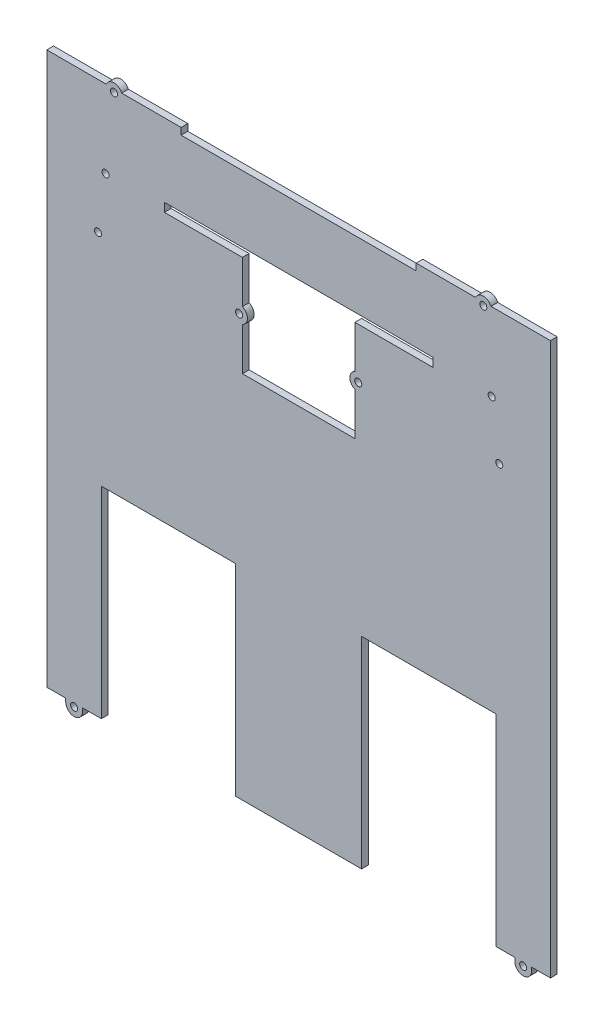
SolidWorks part; units mm, degrees
ref_plane "Plan de face" through (0, 0, 0) normal (0, 0, 1) x (1, 0, 0)
ref_plane "Plan de dessus" through (0, 0, 0) normal (0, 1, 0) x (1, 0, 0)
ref_plane "Plan de droite" through (0, 0, 0) normal (1, 0, 0) x (0, 0, -1)
sketch "Esquisse1" plane through (0, 0, 0) normal (0, 0, 1) x (1, 0, 0)
  line L1 (150, -140) -> (-150, -140)
  line L2 (150, -140) -> (150, 140)
  line L3 (150, 140) -> (-150, 140)
  line L4 (-150, -140) -> (-150, 140)
  line L5 (150, -140) -> (-150, 140) construction
  line L6 (150, 140) -> (-150, -140) construction
  point P0 (0, 0)
  dimension "D1" = 280
  dimension "D2" = 300
extrude "Boss.-Extru.1" add sketch "Esquisse1" along normal blind 4
sketch "Esquisse2" plane through (0, 0, 4) normal (0, 0, 1) x (1, 0, 0)
  line L0 (0, 0) -> (0, -140) construction
  line L1 (-150, -140) -> (150, -140) construction
  line L2 (117.5, -140) -> (117.5, -20)
  line L3 (-37.5, -140) -> (-117.5, -140)
  line L4 (-37.5, -140) -> (-37.5, -20)
  line L5 (-37.5, -20) -> (-117.5, -20)
  line L6 (-117.5, -140) -> (-117.5, -20)
  line L7 (37.5, -20) -> (117.5, -20)
  line L8 (37.5, -140) -> (37.5, -20)
  line L9 (37.5, -140) -> (117.5, -140)
  dimension "D1" = 80
  dimension "D2" = 37.5
  dimension "D3" = 120
extrude "Enlèv. mat.-Extru.1" cut sketch "Esquisse2" against normal through all
sketch "Esquisse4" plane through (0, 0, 0) normal (0, 0, -1) x (-1, 0, 0)
  line L0 (-150, 140) -> (150, 140) construction
  line L1 (-33.5, 140) -> (33.5, 140)
  line L2 (-33.5, 140) -> (-33.5, 80)
  line L3 (-33.5, 80) -> (33.5, 80)
  line L4 (33.5, 140) -> (33.5, 80)
  point P6 (0, 80)
  dimension "D1" = 60
  dimension "D2" = 67
extrude "Enlèv. mat.-Extru.3" cut sketch "Esquisse4" against normal through all
sketch "Esquisse5" plane through (0, 0, 0) normal (0, 0, -1) x (-1, 0, 0)
  line L0 (-133.75, -140) -> (-133.75, -147) construction
  line L1 (-117.5, -140) -> (-150, -140) construction
  line L2 (-128.75, -140) -> (-138.75, -140)
  line L3 (-138.75, -140) -> (-138.75, -142)
  line L4 (-128.75, -140) -> (-128.75, -142)
  line L5 (0, 0) -> (0, -140) construction
  line L6 (-37.5, -140) -> (37.5, -140) construction
  line L7 (133.75, -140) -> (133.75, -147) construction
  line L8 (128.75, -140) -> (128.75, -142)
  line L9 (138.75, -140) -> (138.75, -142)
  line L10 (128.75, -140) -> (138.75, -140)
  arc A0 (-138.75, -142) -> (-128.75, -142) centre (-133.75, -142) ccw
  arc A3 (138.75, -142) -> (128.75, -142) centre (133.75, -142) cw
  line M14 (-150, -140) -> (-117.5, -140)
  line M22 (117.5, -140) -> (150, -140)
  dimension "D2" = 5
  dimension "D3" = 2
extrude "Boss.-Extru.2" add sketch "Esquisse5" against normal blind 4 contours L3 A0 L4 M14 | A3 L9 L8 M22 region at (133.75, -143.0686, 0) region at (-133.75, -143.0686, 0)
sketch "Esquisse6" plane through (0, 0, 0) normal (0, 0, -1) x (-1, 0, 0)
  circle A0 centre (-133.75, -142) radius 2.1
  circle A1 centre (133.75, -142) radius 2.1
  dimension "D1" = 4.2
extrude "Enlèv. mat.-Extru.4" cut sketch "Esquisse6" against normal through all
sketch "Esquisse7" plane through (0, 0, 0) normal (0, 0, -1) x (-1, 0, 0)
  line L0 (-150, 140) -> (-150, 184.8)
  line L1 (-150, 184.8) -> (150, 184.8)
  line L2 (0, 184.8) -> (0, 145.2) construction
  line L3 (80, 145.2) -> (-80, 145.2)
  line L4 (-80, 145.2) -> (-80, 140)
  line L5 (-150, 140) -> (-33.5, 140) construction
  line L6 (-80, 140) -> (-150, 140)
  line L7 (-111.83, -155.2) -> (-81.83, -155.2) construction
  line L8 (80, 140) -> (150, 140)
  line L9 (80, 145.2) -> (80, 140)
  line L10 (150, 140) -> (150, 184.8)
  dimension "D1" = 5.2
  dimension "D2" = 70
  dimension "D3" = 340
extrude "Boss.-Extru.3" add sketch "Esquisse7" against normal blind 4
sketch "Esquisse8" plane through (0, 0, 0) normal (0, 0, -1) x (-1, 0, 0)
  line L0 (0, 184.8) -> (0, 0) construction
  line L1 (150, 184.8) -> (-150, 184.8) construction
  line L2 (-150, 184.8) -> (-150, 188.8)
  line L3 (-150, 188.8) -> (-114.5826, 188.8)
  line L4 (-70, 188.8) -> (-70, 184.8)
  line L5 (-70, 184.8) -> (-150, 184.8)
  line L6 (-105.4174, 188.8) -> (-70, 188.8)
  line L7 (105.4174, 188.8) -> (70, 188.8)
  line L8 (70, 184.8) -> (150, 184.8)
  line L9 (70, 188.8) -> (70, 184.8)
  line L10 (150, 188.8) -> (114.5826, 188.8)
  line L11 (150, 184.8) -> (150, 188.8)
  arc A0 (-114.5826, 188.8) -> (-105.4174, 188.8) centre (-110, 186.8) cw
  arc A1 (114.5826, 188.8) -> (105.4174, 188.8) centre (110, 186.8) ccw
  point P13 (-111.7629, 188.8)
  point P14 (-99.4005, 196.2302)
  point P15 (0, 0)
  point P16 (-110, 184.8)
  point P17 (-95.283, 188.8)
  dimension "D1" = 4
  dimension "D3" = 5
  dimension "D2" = 2
  dimension "D4" = 40
extrude "Boss.-Extru.4" add sketch "Esquisse8" against normal blind 4
sketch "Esquisse9" plane through (0, 0, 0) normal (0, 0, -1) x (-1, 0, 0)
  circle A0 centre (-110, 186.8) radius 2.1
  circle A1 centre (110, 186.8) radius 2.1
  dimension "D1" = 4.2
extrude "Enlèv. mat.-Extru.5" cut sketch "Esquisse9" against normal through all
sketch "Esquisse10" plane through (0, 0, 0) normal (0, 0, -1) x (-1, 0, 0)
  line L0 (80, 142.5) -> (150, 142.5) construction
  line L1 (80, 145.2) -> (80, 140) construction
  line L2 (150, 188.8) -> (150, -140) construction
  line L3 (0, 0) -> (0, 80) construction
  line L4 (-33.5, 80) -> (33.5, 80) construction
  line L5 (33.5, 140) -> (80, 140) construction
  line L6 (-80, 142.5) -> (-150, 142.5) construction
  circle A0 centre (115, 142.5) radius 2.1
  circle A1 centre (-115, 142.5) radius 2.1
  dimension "D1" = 2.5
  dimension "D2" = 4.2
extrude "Enlèv. mat.-Extru.6" cut sketch "Esquisse10" against normal through all
sketch "Esquisse11" plane through (0, 0, 4) normal (0, 0, 1) x (1, 0, 0)
  line L0 (37.5, 112.1) -> (33.5, 107.9) construction
  line L1 (37.5, 107.9) -> (33.5, 107.9) construction
  line L2 (33.5, 140) -> (33.5, 80) construction
  line L3 (37.5, 107.9) -> (33.5, 112.1) construction
  line L4 (37.5, 112.1) -> (33.5, 112.1) construction
  line L5 (121.5, 112.1) -> (117.5, 107.9) construction
  line L6 (117.5, 112.1) -> (121.5, 107.9) construction
  line L7 (121.5, 112.1) -> (117.5, 112.1) construction
  line L8 (0, 0) -> (0, 80) construction
  line L9 (33.5, 80) -> (-33.5, 80) construction
  line L10 (-117.5, 112.1) -> (-121.5, 107.9) construction
  line L11 (-121.5, 112.1) -> (-117.5, 107.9) construction
  line L12 (-37.5, 107.9) -> (-33.5, 112.1) construction
  line L13 (-37.5, 112.1) -> (-33.5, 107.9) construction
  circle A0 centre (35.5, 110) radius 2.1
  circle A1 centre (119.5, 110) radius 2.1
  circle A2 centre (-119.5, 110) radius 2.1
  circle A3 centre (-35.5, 110) radius 2.1
  dimension "D1" = 4.2
extrude "Enlèv. mat.-Extru.7" cut sketch "Esquisse11" against normal through all
sketch "Esquisse12" plane through (0, 0, 0) normal (0, 0, -1) x (-1, 0, 0)
  line L0 (0, 0) -> (0, 80) construction
  line L1 (-33.5, 80) -> (33.5, 80) construction
  circle A0 centre (-35.5, 110) radius 2.1
  circle A1 centre (-35.5, 110) radius 5
  circle A2 centre (35.5, 110) radius 5
  circle A3 centre (35.5, 110) radius 2.1
  dimension "D1" = 4.2
  dimension "D2" = 10
extrude "Boss.-Extru.5" add sketch "Esquisse12" against normal blind 4
